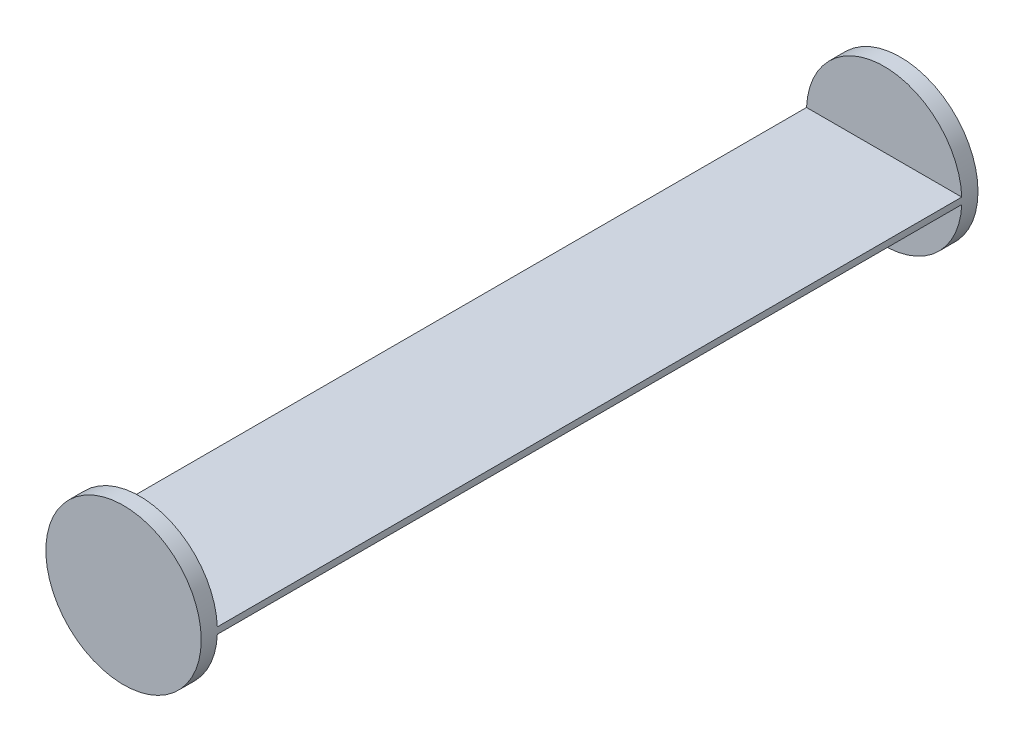
SolidWorks part; units mm, degrees
material "led poid au m3"
ref_plane "Plan de face" through (0, 0, 0) normal (0, 0, 1) x (1, 0, 0)
ref_plane "Plan de dessus" through (0, 0, 0) normal (0, 1, 0) x (1, 0, 0)
ref_plane "Plan de droite" through (0, 0, 0) normal (1, 0, 0) x (0, 0, -1)
sketch "Esquisse1" plane through (0, 0, 0) normal (0, 0, 1) x (1, 0, 0)
  line L1 (23.9792, -1) -> (-23.9792, -1)
  line L3 (23.9792, 1) -> (-23.9792, 1)
  circle A0 centre (0, 0) radius 24
  point P5 (0, -1)
  dimension "D1" = 1
  dimension "D3" = 48
  dimension "D2" = 1
extrude "Boss.-Extru.2" add sketch "Esquisse1" along normal blind 120 and the other way blind 120 contours A0
sketch "Esquisse2" plane through (0, 0, 0) normal (1, 0, 0) x (0, 0, -1)
  line L0 (120, 24) -> (-120, 24) construction
  line L1 (-115, 24) -> (115, 24)
  line L2 (-115, 24) -> (-115, 1)
  line L3 (-115, 1) -> (115, 1)
  line L4 (115, 24) -> (115, 1)
  line L5 (-120, 24) -> (-120, -24) construction
  line L6 (120, -24) -> (120, 24) construction
  dimension "D1" = 1
  dimension "D2" = 5
  dimension "D3" = 5
extrude "Enlèv. mat.-Extru.1" cut sketch "Esquisse2" against normal through all and the other way through all
mirror "Symétrie1" about plane through (0, 0, 0) normal (0, 1, 0) of "Enlèv. mat.-Extru.1"
